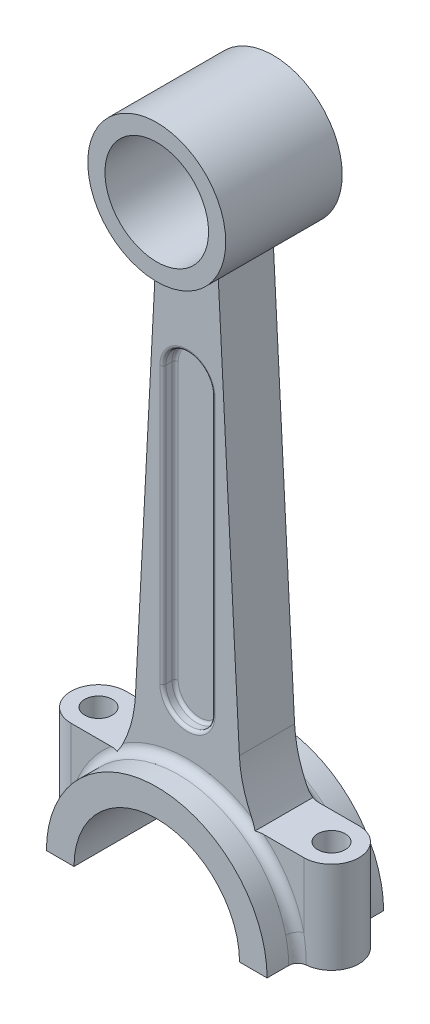
SolidWorks part; units mm, degrees
ref_plane "Front Plane" through (0, 0, 0) normal (0, 0, 1) x (1, 0, 0)
ref_plane "Top Plane" through (0, 0, 0) normal (0, 1, 0) x (1, 0, 0)
ref_plane "Right Plane" through (0, 0, 0) normal (1, 0, 0) x (0, 0, -1)
sketch "Sketch2" plane through (0, 0, 0) normal (0, 0, 1) x (1, 0, 0)
  line L0 (0, 0) -> (0, -201.2) construction
  line L1 (-10, -20.1556) -> (-17.8497, -169.9368)
  line L2 (10, -20.1556) -> (17.8497, -169.9368)
  line L3 (-36, -201.2) -> (-27, -201.2)
  line L4 (27, -201.2) -> (36, -201.2)
  circle A0 centre (0, 0) radius 16.9
  circle A1 centre (0, 0) radius 22.5
  arc A2 (27, -201.2) -> (-27, -201.2) centre (0, -201.2) ccw
  arc A3 (36, -201.2) -> (-36, -201.2) centre (0, -201.2) ccw
  point P14 (0, -201.2)
  dimension "D1" = 33.8
  dimension "D2" = 45
  dimension "D3" = 54
  dimension "D4" = 72
  dimension "D5" = 201.2
  dimension "D6" = 6
  dimension "D7" = 20
extrude "Boss-Extrude1" add sketch "Sketch2" along normal mid plane 38 contours A0 A1 | A3 A2 | L3 A2 L4 A3 region at (-11.5231, 18.5805, 0) region at (0, -166.005, 0)
extrude "Boss-Extrude2" add sketch "Sketch2<4>" along normal mid plane 18 contours A1 L0 A3 L2 | L0 A1 L1 A3 region at (7.1843, -100.8455, 0) region at (-7.1843, -100.8455, 0)
sketch "Sketch2<4>" plane through (0, 0, 0) normal (0, 0, 1) x (1, 0, 0) same geometry as "Sketch2"
sketch "Sketch3" plane through (0, 0, 9) normal (0, 0, 1) x (1, 0, 0)
  line L0 (0, 0) -> (0, -201.2) construction
  line L1 (0, -55.6) -> (0, -145.6) construction
  line L2 (8, -55.6) -> (8, -145.6)
  line L3 (-8, -55.6) -> (-8, -145.6)
  arc A0 (8, -55.6) -> (-8, -55.6) centre (0, -55.6) ccw
  arc A1 (-8, -145.6) -> (8, -145.6) centre (0, -145.6) ccw
  point P6 (0, -100.6)
  dimension "D2" = 8
  dimension "D1" = 90
extrude "Cut-Extrude1" cut sketch "Sketch3" against normal blind 4
mirror "Mirror1" about plane through (0, 0, 0) normal (0, 0, 1) of "Cut-Extrude1"
fillet "Fillet1" radius 1 16 edges at (0, -47.6, -9) (8, -100.6, -9) (0, -153.6, -9) (0, -47.6, -5) (8, -100.6, -5) (0, -153.6, -5) (0, -153.6, 9) (-8, -100.6, 9) (0, -47.6, 9) (0, -153.6, 5) (-8, -100.6, 5) (0, -47.6, 5) (-8, -100.6, -9) (-8, -100.6, -5) (8, -100.6, 9) (8, -100.6, 5)
ref_plane "Plane1" through (0, -171.2, 0) normal (0, 1, 0) x (1, 0, 0)
fillet "Fillet2" radius 40 2 edges at (-17.8497, -169.9368, 0) (17.8497, -169.9368, 0)
sketch "Sketch5" plane through (0, -171.2, 0) normal (0, 1, 0) x (1, 0, 0)
  line L0 (-38, 0) -> (38, 0) construction
  line L1 (-38, 9) -> (38, 9)
  line L2 (-38, -9) -> (38, -9)
  arc A0 (-38, 9) -> (-38, -9) centre (-38, 0) ccw
  arc A1 (38, -9) -> (38, 9) centre (38, 0) ccw
  point P2 (0, 0)
  dimension "D2" = 9
  dimension "D1" = 76
extrude "Boss-Extrude3" add sketch "Sketch5" against normal up to surface (30 mm away) up to face at (-31.5, -201.2, 0)
sketch "Sketch6" plane through (0, 0, 9) normal (0, 0, 1) x (1, 0, 0)
  line L1 (-27, -201.2) -> (27, -201.2)
  line L2 (-27, -201.2) -> (27, -201.2)
  arc A1 (27, -201.2) -> (-27, -201.2) centre (0, -201.2) ccw
  arc A2 (27, -201.2) -> (-27, -201.2) centre (0, -201.2) ccw
  dimension "D1" = 0
extrude "Cut-Extrude2" cut sketch "Sketch6" against normal through all both and the other way through all
sketch "Sketch7" plane through (0, -171.2, 0) normal (0, 1, 0) x (1, 0, 0)
  circle A0 centre (38, 0) radius 4.5
  circle A1 centre (-38, 0) radius 4.5
  dimension "D1" = 9
  dimension "D2" = 9
extrude "Cut-Extrude3" cut sketch "Sketch7" against normal through all and the other way through all
fillet "Fillet5" radius 3 2 edges at (0, -165.2, 9) (0, -165.2, -9)
